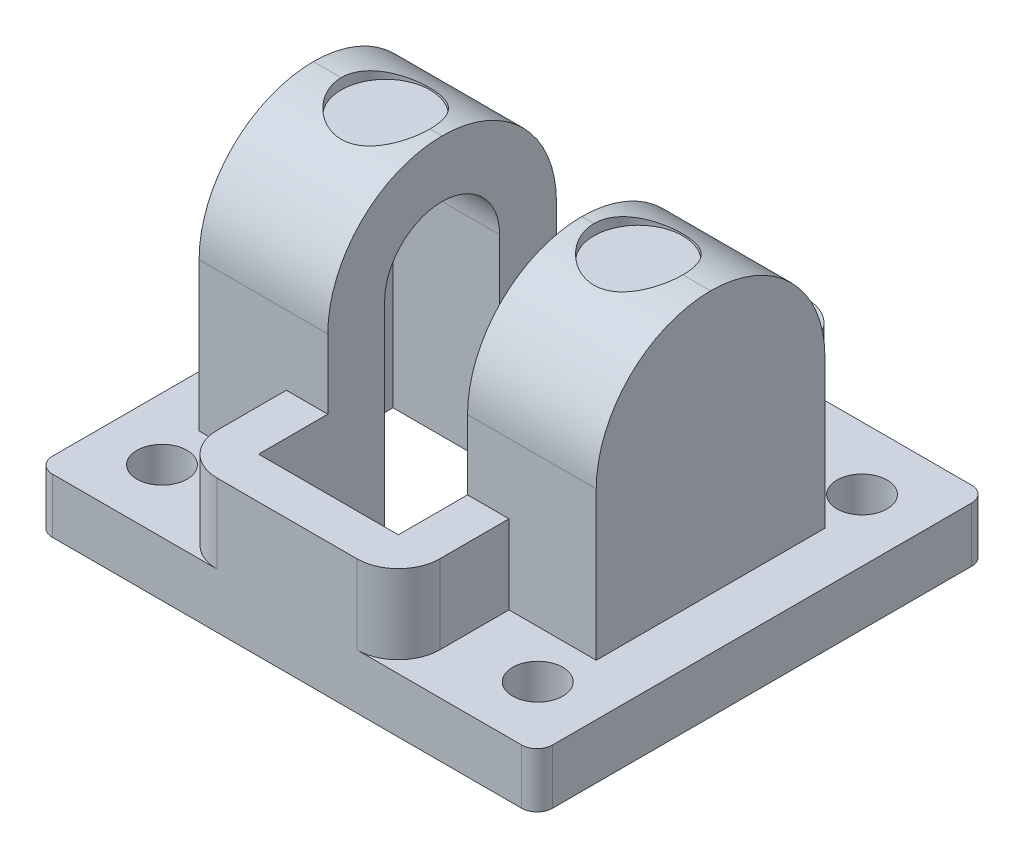
SolidWorks part; units mm, degrees
ref_plane "Front Plane" through (0, 0, 0) normal (0, 0, 1) x (1, 0, 0)
ref_plane "Top Plane" through (0, 0, 0) normal (0, 1, 0) x (1, 0, 0)
ref_plane "Right Plane" through (0, 0, 0) normal (1, 0, 0) x (0, 0, -1)
sketch "Sketch2" plane through (0, 0, 0) normal (0, 1, 0) x (1, 0, 0)
  line L0 (2.6543, 8.5471) -> (2.6543, 6.9723) construction
  line L1 (-9.4996, -8.5471) -> (9.4996, -8.5471)
  line L2 (-9.4996, -8.5471) -> (-9.4996, 8.5471)
  line L3 (-9.4996, 8.5471) -> (9.4996, 8.5471)
  line L4 (9.4996, -8.5471) -> (9.4996, 8.5471)
  line L5 (-9.4996, -8.5471) -> (9.4996, 8.5471) construction
  line L6 (-9.4996, 8.5471) -> (9.4996, -8.5471) construction
  line L7 (-6.0325, -6.0325) -> (6.0325, -6.0325) construction
  line L8 (-6.0325, -6.0325) -> (-6.0325, 6.0325) construction
  line L9 (-6.0325, 6.0325) -> (6.0325, 6.0325) construction
  line L10 (6.0325, -6.0325) -> (6.0325, 6.0325) construction
  line L11 (-6.0325, -6.0325) -> (6.0325, 6.0325) construction
  line L12 (-6.0325, 6.0325) -> (6.0325, -6.0325) construction
  line L13 (-6.985, -5.08) -> (6.985, -5.08) construction
  line L14 (-6.985, -5.08) -> (-6.985, 5.08) construction
  line L15 (-6.985, 5.08) -> (6.985, 5.08) construction
  line L16 (6.985, -5.08) -> (6.985, 5.08) construction
  line L17 (-6.985, -5.08) -> (6.985, 5.08) construction
  line L18 (-6.985, 5.08) -> (6.985, -5.08) construction
  line L19 (-2.6543, -6.9723) -> (2.6543, -6.9723)
  line L20 (-2.6543, -6.9723) -> (-2.6543, 6.9723)
  line L21 (-2.6543, 6.9723) -> (2.6543, 6.9723)
  line L22 (2.6543, -6.9723) -> (2.6543, 6.9723)
  line L23 (-2.6543, -6.9723) -> (2.6543, 6.9723) construction
  line L24 (-2.6543, 6.9723) -> (2.6543, -6.9723) construction
  line L25 (-4.2291, -8.5471) -> (4.2291, -8.5471)
  line L26 (-4.2291, -8.5471) -> (-4.2291, 8.5471)
  line L27 (-4.2291, 8.5471) -> (4.2291, 8.5471)
  line L28 (4.2291, -8.5471) -> (4.2291, 8.5471)
  line L29 (-4.2291, -8.5471) -> (4.2291, 8.5471) construction
  line L30 (-4.2291, 8.5471) -> (4.2291, -8.5471) construction
  line L31 (2.6543, 6.9723) -> (4.2291, 6.9723) construction
  line L32 (7.9375, 6.0325) -> (6.985, 6.0325) construction
  line L33 (-7.5438, 4.3434) -> (7.5438, 4.3434)
  line L34 (-7.5438, 4.3434) -> (-7.5438, -4.3434)
  line L35 (-7.5438, -4.3434) -> (7.5438, -4.3434)
  line L36 (7.5438, 4.3434) -> (7.5438, -4.3434)
  line L37 (-7.5438, 4.3434) -> (7.5438, -4.3434) construction
  line L38 (-7.5438, -4.3434) -> (7.5438, 4.3434) construction
  circle A0 centre (6.985, -6.0325) radius 0.9525 construction
  circle A1 centre (6.985, 6.0325) radius 0.9525 construction
  circle A2 centre (-6.985, 6.0325) radius 0.9525 construction
  circle A3 centre (-6.985, -6.0325) radius 0.9525 construction
  circle A4 centre (7.1374, 6.1595) radius 0.9525
  circle A5 centre (7.1374, -6.1595) radius 0.9525
  circle A6 centre (-7.1374, -6.1595) radius 0.9525
  circle A7 centre (-7.1374, 6.1595) radius 0.9525
  circle A8 centre (7.1374, 6.1595) radius 1.5875 construction
  circle A9 centre (7.1374, -6.1595) radius 1.5875 construction
  circle A10 centre (-7.1374, -6.1595) radius 1.5875 construction
  circle A11 centre (-7.1374, 6.1595) radius 1.5875 construction
  point P0 (0, 0)
  point P5 (0, 0)
  point P19 (0, 0)
  point P24 (0, 0)
  point P27 (0, 0)
  point P34 (0, 0)
  dimension "D3" = 12.065
  dimension "D5" = 1.905
  dimension "D1" = 18.9992
  dimension "D2" = 17.0942
  dimension "D4" = 10.16
  dimension "D6" = 8.4582
  dimension "D7" = 1.5748
  dimension "D8" = 15.0876
  dimension "D9" = 8.6868
extrude "Boss-Extrude1" add sketch "Sketch2" along normal blind 2.0828 contours L35 L34 L33 L26 L3 L2 L1 A3 A2 | L33 L36 L35 L28 L1 L4 L3 A1 A0 | L35 L26 L1 L28 L22 L19 L20 | L35 L20 L19 L22 | L26 L35 L20 L33 | L20 L35 L22 L33 | L22 L35 L28 L33 | L36 L33 L28 L35 | L34 L35 L26 L33 | L20 L33 L22 L21 | L26 L33 L20 L21 L22 L28 L3 region at (-9.3207, 0, 0) region at (-4.1346, 0, 6.4452) region at (4.408, 0, 6.4452) region at (-5.8864, 0, 0) region at (-3.4417, 0, 0) region at (0, 0, -8.4526) region at (3.4417, 0, 0) region at (5.8865, 0, 0) region at (0, 0, 5.6578) region at (0, 0, 0) region at (0, 0, -5.6579)
extrude "Boss-Extrude2" add sketch "Sketch2<3>" along normal blind 2.9972 from surface contours L26 L33 L20 L21 L22 L28 L3 | L26 L35 L20 L33 | L22 L35 L28 L33 | L35 L26 L1 L28 L22 L19 L20 | L20 L33 L22 L21 | L20 L35 L22 L33 | L35 L20 L19 L22 region at (-4.1346, 0, 6.4452) region at (-3.4417, 0, 0) region at (0, 0, -8.4526) region at (3.4417, 0, 0) region at (0, 0, 5.6578) region at (0, 0, 0) region at (0, 0, -5.6579) starting at face at (0, 2.0828, 0)
sketch "Sketch2<3>" plane through (0, 0, 0) normal (0, 1, 0) x (1, 0, 0) same geometry as "Sketch2"
extrude "Boss-Extrude3" add sketch "Sketch2<4>" along normal blind 9.9822 from surface contours L36 L33 L28 L35 | L34 L35 L26 L33 region at (-5.8864, 0, 0) region at (5.8865, 0, 0) starting at face at (7.1374, 2.0828, -5.207)
sketch "Sketch2<4>" plane through (0, 0, 0) normal (0, 1, 0) x (1, 0, 0) same geometry as "Sketch2"
extrude "Boss-Extrude4" add sketch "Sketch2<6>" along normal up to surface (12.065 mm away) from surface contours L26 L35 L20 L33 | L22 L35 L28 L33 region at (-3.4417, 0, 0) region at (3.4417, 0, 0) up to face at (-5.8864, 12.065, 0) starting at face at (6.3754, 2.0828, 0)
sketch "Sketch2<6>" plane through (0, 0, 0) normal (0, 1, 0) x (1, 0, 0) same geometry as "Sketch2"
extrude "Cut-Extrude1" cut sketch "Sketch2<5>" along normal up to next contours L20 L33 L22 L21 | L20 L35 L22 L33 | L35 L20 L19 L22 region at (0, 0, 5.6578) region at (0, 0, 0) region at (0, 0, -5.6579)
sketch "Sketch2<5>" plane through (0, 0, 0) normal (0, 1, 0) x (1, 0, 0) same geometry as "Sketch2"
sketch "Sketch4" plane through (0, 0, 0) normal (0, 1, 0) x (1, 0, 0)
  line L1 (-6.7056, -2.1844) -> (6.7056, -2.1844)
  line L2 (-6.7056, -2.1844) -> (-6.7056, 2.1844)
  line L3 (-6.7056, 2.1844) -> (6.7056, 2.1844)
  line L4 (6.7056, -2.1844) -> (6.7056, 2.1844)
  line L5 (-6.7056, -2.1844) -> (6.7056, 2.1844) construction
  line L6 (-6.7056, 2.1844) -> (6.7056, -2.1844) construction
  point P0 (0, 0)
  dimension "D1" = 4.3688
  dimension "D2" = 13.4112
extrude "Cut-Extrude2" cut sketch "Sketch4" along normal blind 9.906
fillet "Fillet1" radius 2.1844 4 edges at (4.68, 9.906, -2.1844) (4.68, 9.906, 2.1844) (-4.6799, 9.906, 2.1844) (-4.6799, 9.906, -2.1844)
fillet "Fillet2" radius 4.3434 4 edges at (-5.099, 12.065, 4.3434) (-5.099, 12.065, -4.3434) (5.0991, 12.065, 4.3434) (5.0991, 12.065, -4.3434)
fillet "Fillet3" radius 1.5748 4 edges at (4.2291, 3.5814, 8.5471) (-4.2291, 3.5814, 8.5471) (4.2291, 3.5814, -8.5471) (-4.2291, 3.5814, -8.5471)
fillet "Fillet4" radius 0.5842 4 edges at (9.4996, 1.0414, 8.5471) (9.4996, 1.0414, -8.5471) (-9.4996, 1.0414, -8.5471) (-9.4996, 1.0414, 8.5471)
ref_plane "Plane1" through (0, 12.065, 0) normal (0, 1, 0) x (1, 0, 0)
sketch "Sketch6" plane through (0, 12.065, 0) normal (0, 1, 0) x (1, 0, 0)
  line L0 (7.5438, 0) -> (2.6543, 0) construction
  line L1 (3.1115, 0) -> (0, 0) construction
  line L4 (-2.6543, 0) -> (-7.5438, 0) construction
  line L5 (0, 0) -> (-3.1115, 0) construction
  circle A0 centre (4.8006, 0) radius 1.6891
  circle A1 centre (-4.8006, 0) radius 1.6891
  dimension "D1" = 6.223
  dimension "D2" = 3.3782
extrude "Cut-Extrude3" cut sketch "Sketch6" against normal blind 0.4064
